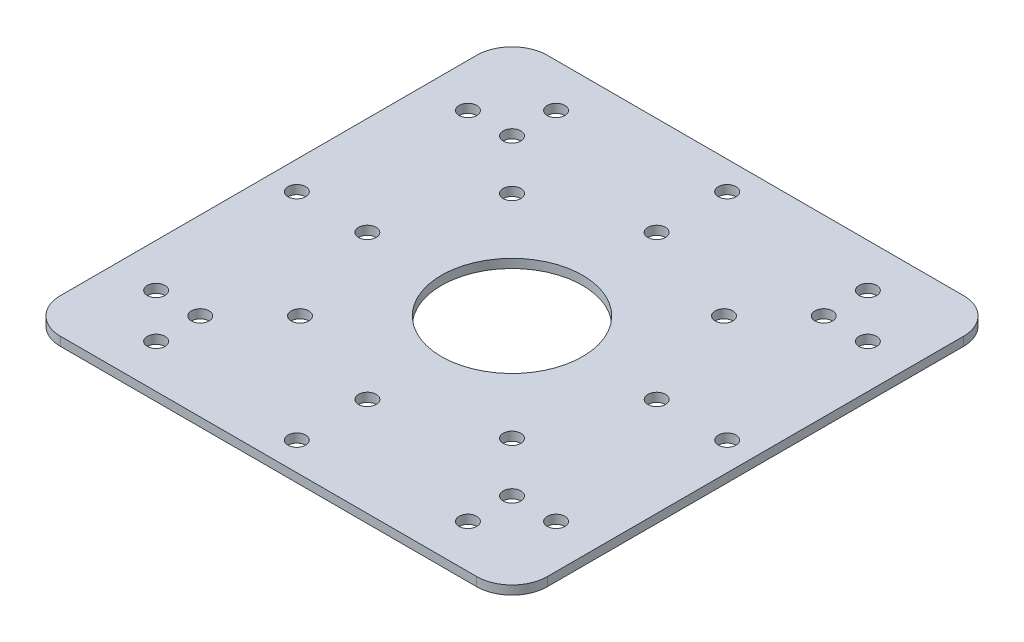
SolidWorks part; units mm, degrees
ref_plane "Front Plane" through (0, 0, 0) normal (0, 0, 1) x (1, 0, 0)
ref_plane "Top Plane" through (0, 0, 0) normal (0, 1, 0) x (1, 0, 0)
ref_plane "Right Plane" through (0, 0, 0) normal (1, 0, 0) x (0, 0, -1)
sketch "Sketch1" plane through (0, 0, 0) normal (0, 1, 0) x (1, 0, 0)
  line L1 (29.972, -35.052) -> (-29.972, -35.052)
  line L2 (35.052, -29.972) -> (35.052, 29.972)
  line L3 (29.972, 35.052) -> (-29.972, 35.052)
  line L4 (-35.052, -29.972) -> (-35.052, 29.972)
  line L5 (35.052, -35.052) -> (-35.052, 35.052) construction
  line L6 (35.052, 35.052) -> (-35.052, -35.052) construction
  arc A0 (-35.052, -29.972) -> (-29.972, -35.052) centre (-29.972, -29.972) ccw
  arc A1 (29.972, -35.052) -> (35.052, -29.972) centre (29.972, -29.972) ccw
  arc A2 (35.052, 29.972) -> (29.972, 35.052) centre (29.972, 29.972) ccw
  arc A3 (-29.972, 35.052) -> (-35.052, 29.972) centre (-29.972, 29.972) ccw
  point P0 (0, 0)
  dimension "D3" = 5.08
  dimension "D1" = 70.104
  dimension "D2" = 70.104
extrude "Boss-Extrude1" add sketch "Sketch1" along normal blind 1.27
sketch "Sketch2" plane through (0, 1.27, 0) normal (0, 1, 0) x (1, 0, 0)
  circle A0 centre (0, 0) radius 10.16
  circle A1 centre (20.8338, 0) radius 1.27
  circle A2 centre (30.988, 0) radius 1.27
  circle A3 centre (-20.8338, 0) radius 1.27
  circle A4 centre (-30.988, 0) radius 1.27
  circle A5 centre (0, -20.828) radius 1.27
  circle A6 centre (0, -30.988) radius 1.27 construction
  circle A7 centre (0, 20.828) radius 1.27
  circle A8 centre (0, 30.988) radius 1.27
  circle A9 centre (-15.2664, -15.2664) radius 1.27
  circle A10 centre (-22.4506, -22.4506) radius 1.27
  circle A11 centre (-28.8006, -22.4506) radius 1.27
  circle A12 centre (-22.4506, -28.8006) radius 1.27
  circle A13 centre (28.8006, -22.4506) radius 1.27
  circle A14 centre (22.4506, -28.8006) radius 1.27
  circle A15 centre (22.4506, -22.4506) radius 1.27
  circle A16 centre (15.2664, -15.2664) radius 1.27
  circle A17 centre (28.8006, 22.4506) radius 1.27
  circle A18 centre (22.4506, 28.8006) radius 1.27
  circle A19 centre (22.4506, 22.4506) radius 1.27
  circle A20 centre (15.2664, 15.2664) radius 1.27
  circle A21 centre (-22.4506, 28.8006) radius 1.27
  circle A22 centre (-28.8006, 22.4506) radius 1.27
  circle A23 centre (-15.2664, 15.2664) radius 1.27
  circle A24 centre (-22.4506, 22.4506) radius 1.27
  circle A25 centre (0, 30.988) radius 1.27
  circle A26 centre (0, -30.988) radius 1.27
  dimension "D1" = 20.32
  dimension "D2" = 0
extrude "Cut-Extrude1" cut sketch "Sketch2" against normal through all
